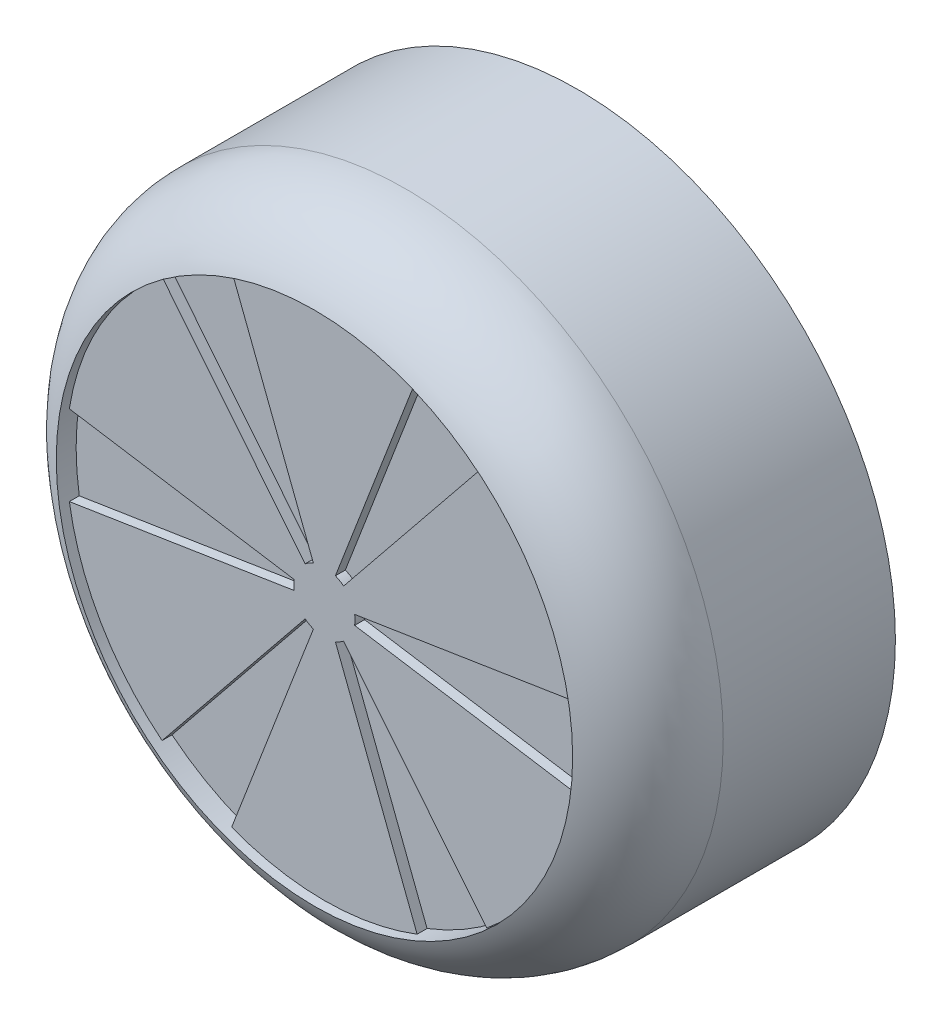
SolidWorks part; units mm, degrees
ref_plane "前视基准面" through (0, 0, 0) normal (0, 0, 1) x (1, 0, 0)
ref_plane "上视基准面" through (0, 0, 0) normal (0, 1, 0) x (1, 0, 0)
ref_plane "右视基准面" through (0, 0, 0) normal (1, 0, 0) x (0, 0, -1)
sketch "草图1" plane through (0, 0, 0) normal (0, 0, 1) x (1, 0, 0)
  circle A0 centre (0, 0) radius 32
extrude "凸台-拉伸1" add sketch "草图1" along normal blind 26.5
sketch "草图2" plane through (0, 0, 26.5) normal (0, 0, 1) x (1, 0, 0)
  line L0 (0, 0) -> (35.4582, 0) construction
  line L1 (25.6834, 4.0454) -> (0, 0)
  line L2 (0, 0) -> (25.6834, -4.0454)
  line L3 (16.3451, -20.2198) -> (0, 0)
  line L4 (0, 0) -> (9.3383, -24.2651)
  line L5 (-9.3383, -24.2651) -> (0, 0)
  line L6 (0, 0) -> (-16.3451, -20.2198)
  line L7 (-25.6834, -4.0454) -> (0, 0)
  line L8 (0, 0) -> (-25.6834, 4.0454)
  line L9 (-16.3451, 20.2198) -> (0, 0)
  line L10 (0, 0) -> (-9.3383, 24.2651)
  line L11 (9.3383, 24.2651) -> (0, 0)
  line L12 (0, 0) -> (16.3451, 20.2198)
  arc A0 (25.6834, -4.0454) -> (25.6834, 4.0454) centre (0, 0) ccw
  arc A1 (9.3383, -24.2651) -> (16.3451, -20.2198) centre (0, 0) ccw
  arc A2 (-16.3451, -20.2198) -> (-9.3383, -24.2651) centre (0, 0) ccw
  arc A3 (-25.6834, 4.0454) -> (-25.6834, -4.0454) centre (0, 0) ccw
  arc A4 (-9.3383, 24.2651) -> (-16.3451, 20.2198) centre (0, 0) ccw
  arc A5 (16.3451, 20.2198) -> (9.3383, 24.2651) centre (0, 0) ccw
  circle A6 centre (0, 0) radius 3.083
  point P17 (0, 0)
  dimension "D1" = 6
extrude "切除-拉伸4" cut sketch "草图2" against normal blind 2 contours A6 L10 A4 L9 | A6 L12 A5 L11 | A6 L0 A0 L1 | L0 A6 L2 A0 | A6 L4 A1 L3 | A6 L6 A2 L5 | A6 L8 A3 L7 region at (17.4799, 1.3682, 26.5) region at (17.4799, -1.3682, 26.5) region at (8.74, -15.138, 26.5) region at (-8.74, -15.138, 26.5) region at (-17.4799, 0, 26.5) region at (-8.74, 15.138, 26.5) region at (8.74, 15.138, 26.5)
sketch "草图3" plane through (0, 0, 26.5) normal (0, 0, 1) x (1, 0, 0)
  circle A0 centre (0, 0) radius 26
extrude "切除-拉伸5" cut sketch "草图3" against normal blind 1
fillet "圆角1" radius 10 1 edges at (32, 0, 26.5)
sketch "草图4" plane through (0, 0, 0) normal (0, 0, -1) x (-1, 0, 0)
  circle A0 centre (0, 0) radius 6.6886
extrude "切除-拉伸6" cut sketch "草图4" against normal blind 5
